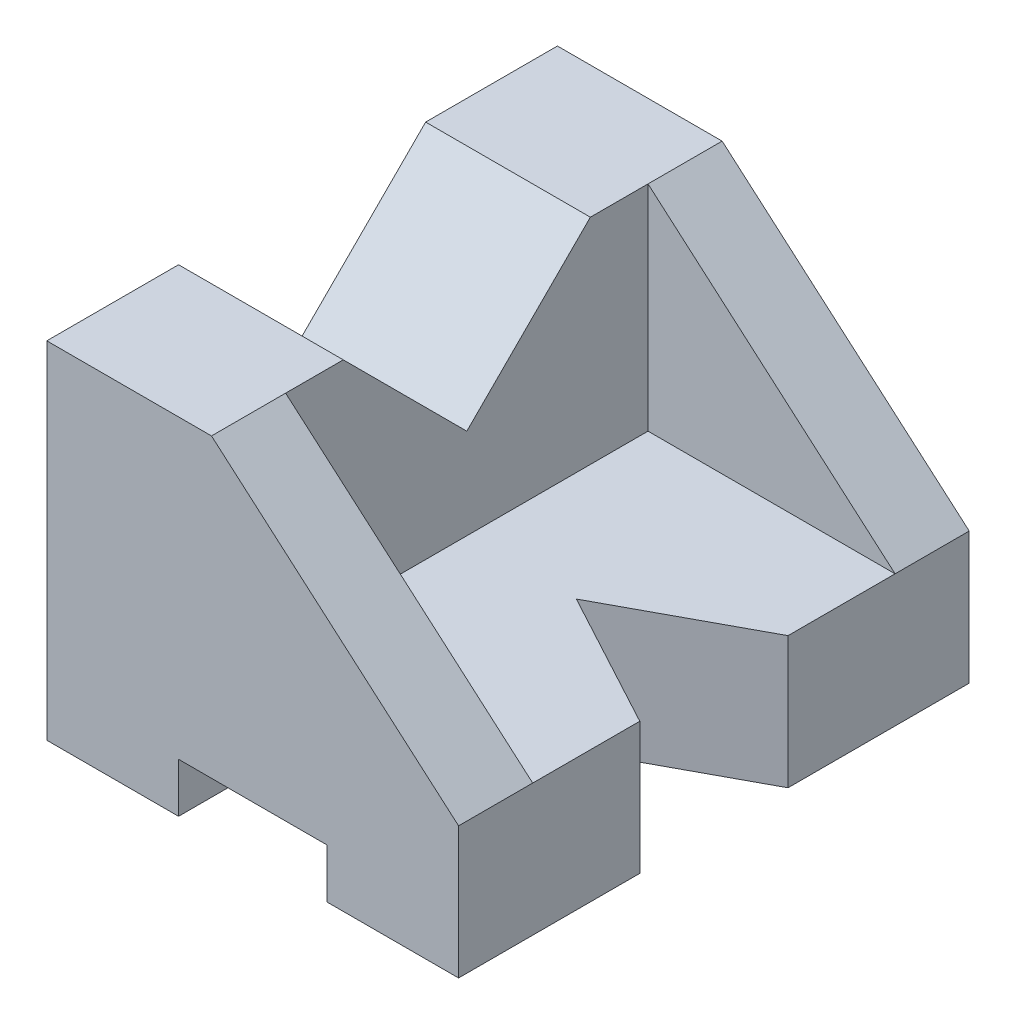
SolidWorks part; units mm, degrees
ref_plane "Front Plane" through (0, 0, 0) normal (0, 0, 1) x (1, 0, 0)
ref_plane "Top Plane" through (0, 0, 0) normal (0, 1, 0) x (1, 0, 0)
ref_plane "Right Plane" through (0, 0, 0) normal (1, 0, 0) x (0, 0, -1)
sketch "Sketch1" plane through (0, 0, 0) normal (0, 0, 1) x (1, 0, 0)
  line L0 (0, 0) -> (0, 42)
  line L1 (0, 42) -> (20, 42)
  line L2 (20, 42) -> (20, 16)
  line L3 (20, 16) -> (50, 16)
  line L4 (50, 16) -> (50, 0)
  line L5 (50, 0) -> (34, 0)
  line L6 (34, 0) -> (34, 6)
  line L7 (34, 6) -> (16, 6)
  line L8 (16, 6) -> (16, 0)
  line L9 (16, 0) -> (0, 0)
  line L10 (50, 16) -> (20, 42)
  dimension "D1" = 16
  dimension "D2" = 50
  dimension "D3" = 42
  dimension "D4" = 20
  dimension "D5" = 6
extrude "Boss-Extrude1" add sketch "Sketch1" along normal mid plane 62 contours L9 L8 L7 L6 L5 L4 L3 L2 L1 L0 region at (18.5644, 17.4554, 0)
extrude "Boss-Extrude3" add sketch "Sketch1<7>" along normal blind 9 from offset 22 contours L3 L10 L2 region at (30, 24.6667, 0)
sketch "Sketch1<7>" plane through (0, 0, 0) normal (0, 0, 1) x (1, 0, 0) same geometry as "Sketch1"
extrude "Boss-Extrude4" add sketch "Sketch1<8>" against normal blind 9 from offset 22 contours L3 L10 L2 region at (30, 24.6667, 0) offset against normal yes
sketch "Sketch1<8>" plane through (0, 0, 0) normal (0, 0, 1) x (1, 0, 0) same geometry as "Sketch1"
sketch "Sketch2" plane through (20, 0, 0) normal (1, 0, 0) x (0, 0, -1)
  line L0 (-15, 42) -> (0, 27)
  line L1 (-22, 42) -> (22, 42) construction
  line L2 (0, 27) -> (15, 42)
  line L5 (22, 16) -> (22, 42) construction
  line L6 (-15, 42) -> (15, 42)
  dimension "D1" = 16
  dimension "D2" = 30
  dimension "D3" = 22
extrude "Cut-Extrude1" cut sketch "Sketch2" against normal up to next
sketch "Sketch3" plane through (0, 16, 0) normal (0, 1, 0) x (1, 0, 0)
  line L0 (50, 9) -> (33.3005, 0)
  line L1 (50, -22) -> (50, 22) construction
  line L2 (33.3005, 0) -> (50, -9)
  line L3 (50, 9) -> (50, -9)
  line L6 (50, 22) -> (20, 22) construction
  dimension "D1" = 22
  dimension "D2" = 16.6995
  dimension "D3" = 18
extrude "Cut-Extrude2" cut sketch "Sketch3" against normal up to next
